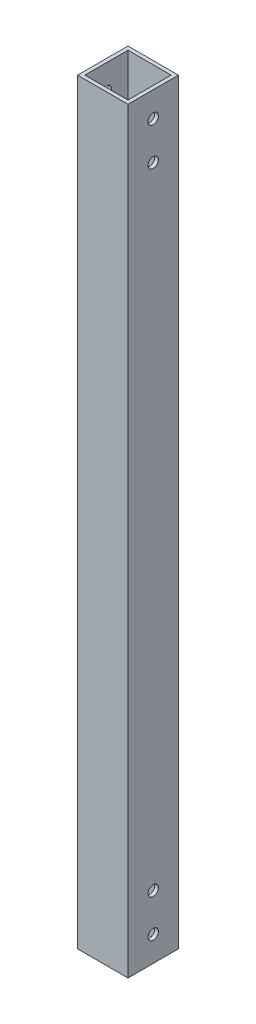
SolidWorks part; units mm, degrees
ref_plane "Front Plane" through (0, 0, 0) normal (0, 0, 1) x (1, 0, 0)
ref_plane "Top Plane" through (0, 0, 0) normal (0, 1, 0) x (1, 0, 0)
ref_plane "Right Plane" through (0, 0, 0) normal (1, 0, 0) x (0, 0, -1)
sketch "Sketch1" plane through (0, 0, 0) normal (0, 1, 0) x (1, 0, 0)
  line L0 (1.45, 18.55) -> (18.55, 18.55)
  line L1 (0, 0) -> (20, 0)
  line L2 (0, 0) -> (0, 20)
  line L3 (0, 20) -> (20, 20)
  line L4 (20, 0) -> (20, 20)
  line L5 (18.55, 1.45) -> (18.55, 18.55)
  line L6 (1.45, 1.45) -> (18.55, 1.45)
  line L7 (1.45, 1.45) -> (1.45, 18.55)
  dimension "D1" = 20
  dimension "D2" = 1.45
extrude "Boss-Extrude1" add sketch "Sketch1" along normal blind 300
sketch "Sketch2" plane through (0, 0, 0) normal (-1, 0, 0) x (0, 0, 1)
  line L0 (-20, 300) -> (-20, 0) construction
  line L1 (-20, 300) -> (0, 300) construction
  line L2 (-20, 0) -> (0, 0) construction
  circle A0 centre (-10, 290) radius 2.05
  circle A1 centre (-10, 275) radius 2.05
  circle A2 centre (-10, 25) radius 2.05
  circle A3 centre (-10, 10) radius 2.05
  point P8 (0, 0)
  dimension "D1" = 4.1
  dimension "D2" = 15
  dimension "D3" = 15
  dimension "D4" = 10
  dimension "D5" = 10
  dimension "D6" = 10
extrude "Cut-Extrude1" cut sketch "Sketch2" against normal through all
